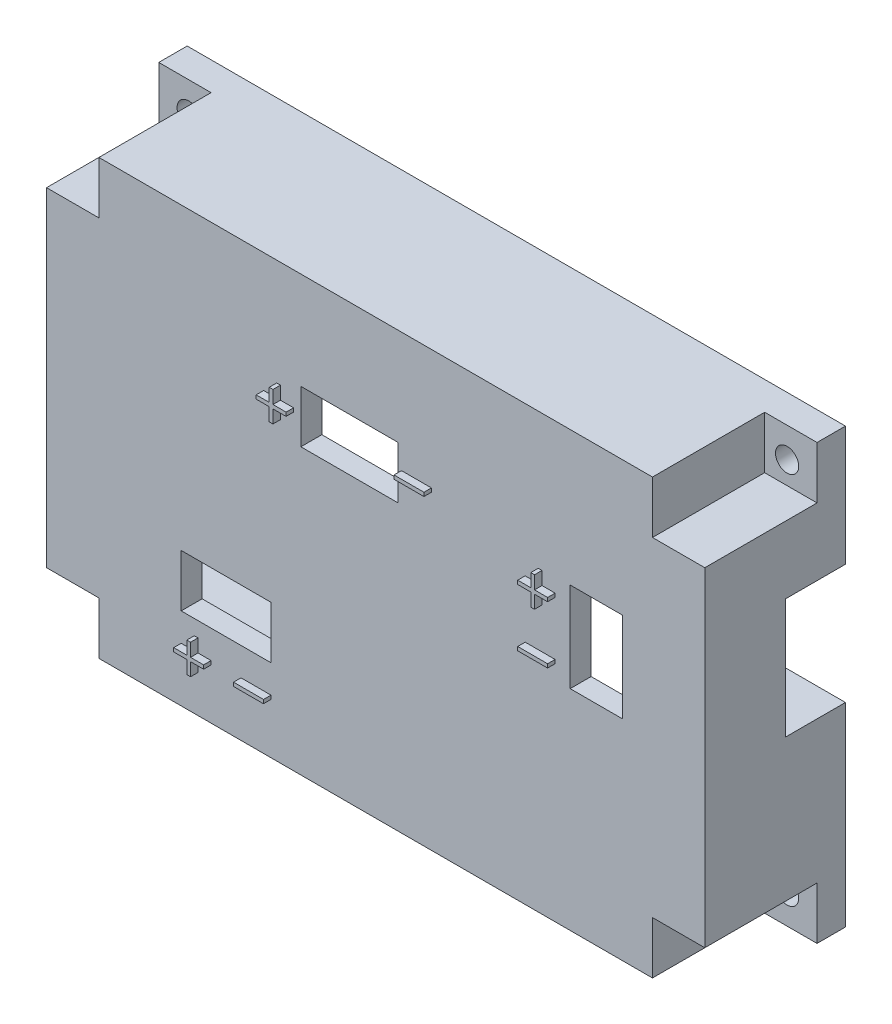
SolidWorks part; units mm, degrees
ref_plane "前视基准面" through (0, 0, 0) normal (0, 0, 1) x (1, 0, 0)
ref_plane "上视基准面" through (0, 0, 0) normal (0, 1, 0) x (1, 0, 0)
ref_plane "右视基准面" through (0, 0, 0) normal (1, 0, 0) x (0, 0, -1)
other "Configuration Table"
sketch "草图1" plane through (0, 0, 0) normal (0, 0, 1) x (1, 0, 0)
  line L1 (0, 58) -> (88, 58)
  line L2 (0, 58) -> (0, 0)
  line L3 (0, 0) -> (88, 0)
  line L4 (88, 58) -> (88, 0)
  dimension "D1" = 88
  dimension "D2" = 58
extrude "凸台-拉伸1" add sketch "草图1" along normal blind 18.8
sketch "草图2" plane through (0, 0, 18.8) normal (0, 0, 1) x (1, 0, 0)
  line L0 (88, 58) -> (0, 58) construction
  line L1 (0, 58) -> (7, 58)
  line L2 (0, 58) -> (0, 51)
  line L3 (0, 51) -> (7, 51)
  line L4 (7, 58) -> (7, 51)
  line L5 (0, 29) -> (88, 29) construction
  line L8 (44, 58) -> (44, 20.983) construction
  line L9 (0, 7) -> (7, 7)
  line L10 (7, 0) -> (7, 7)
  line L11 (0, 0) -> (7, 0)
  line L12 (0, 0) -> (0, 7)
  line L13 (88, 0) -> (88, 7)
  line L14 (88, 0) -> (81, 0)
  line L15 (81, 0) -> (81, 7)
  line L16 (88, 7) -> (81, 7)
  line L17 (88, 51) -> (81, 51)
  line L18 (81, 58) -> (81, 51)
  line L19 (88, 58) -> (81, 58)
  line L20 (88, 58) -> (88, 51)
  dimension "D1" = 7
  dimension "D2" = 7
extrude "切除-拉伸1" cut sketch "草图2" against normal blind 15
sketch "草图3" plane through (0, 0, 3.8) normal (0, 0, 1) x (1, 0, 0)
  line L0 (7, 58) -> (0, 58) construction
  line L1 (0, 58) -> (0, 51) construction
  line L2 (0, 29) -> (42.1109, 29) construction
  line L4 (44, 58) -> (44, 16.8363) construction
  circle A0 centre (4, 54) radius 1.55
  circle A1 centre (4, 4) radius 1.55
  circle A2 centre (84, 4) radius 1.55
  circle A3 centre (84, 54) radius 1.55
  dimension "D1" = 4
  dimension "D2" = 4
extrude "切除-拉伸2" cut sketch "草图3" against normal blind 3
sketch "草图4" plane through (0, 0, 0) normal (0, 0, -1) x (-1, 0, 0)
  line L8 (-8, 8) -> (-8, 50)
  line L9 (-8, 50) -> (-80, 50)
  line L10 (-80, 50) -> (-80, 8)
  line L11 (-80, 8) -> (-8, 8)
  line L12 (-8, 8) -> (-8, 50)
  line L13 (-8, 50) -> (-80, 50)
  line L14 (-80, 50) -> (-80, 8)
  line L15 (-80, 8) -> (-8, 8)
  dimension "D1" = 8
extrude "切除-拉伸6" cut sketch "草图4" against normal blind 16
sketch "草图6" plane through (0, 0, 0) normal (0, -1, 0) x (1, 0, 0)
  line L0 (0, 0) -> (88, 0) construction
  line L1 (16, 8) -> (32, 8)
  line L2 (16, 8) -> (16, 0)
  line L3 (16, 0) -> (32, 0)
  line L4 (32, 8) -> (32, 0)
  line L5 (0, 3.8) -> (0, 18.8) construction
  dimension "D1" = 16
  dimension "D2" = 32
  dimension "D3" = 8
extrude "切除-拉伸7" cut sketch "草图6" against normal blind 8
sketch "草图7" plane through (0, 0, 18.8) normal (0, 0, 1) x (1, 0, 0)
  line L103 (18, 18) -> (30, 18)
  line L104 (18, 18) -> (18, 11)
  line L105 (18, 11) -> (30, 11)
  line L106 (30, 18) -> (30, 11)
  line L107 (70, 40) -> (77, 40)
  line L108 (70, 40) -> (70, 28)
  line L109 (70, 28) -> (77, 28)
  line L110 (77, 40) -> (77, 28)
  line L111 (34, 45) -> (47, 45)
  line L112 (34, 45) -> (34, 38)
  line L113 (34, 38) -> (47, 38)
  line L114 (80, 8) -> (80, 50)
  line L115 (8, 8) -> (80, 8)
  line L116 (8, 50) -> (8, 8)
  line L117 (80, 50) -> (8, 50)
  line L118 (80, 8) -> (80, 50)
  line L119 (8, 8) -> (80, 8)
  line L120 (8, 50) -> (8, 8)
  line L121 (80, 50) -> (8, 50)
  line L122 (47, 45) -> (47, 38)
  dimension "D2" = 10
  dimension "D3" = 22
  dimension "D4" = 3
  dimension "D5" = 10
  dimension "D6" = 10
  dimension "D7" = 22
  dimension "D8" = 3
  dimension "D9" = 10
  dimension "D10" = 26
  dimension "D11" = 39
  dimension "D12" = 5
  dimension "D13" = 12
  dimension "D1" = 8
extrude "切除-拉伸11" cut sketch "草图7" against normal up to next contours L122 L111 L112 L113 | L110 L107 L108 L109 | L104 L103 L106 L105 region at (73.5, 34, 18.8) region at (40.5, 41.5, 18.8)
sketch "草图10" plane through (88, 0, 0) normal (1, 0, 0) x (0, 0, -1)
  line L0 (0, 0) -> (0, 58) construction
  line L1 (-8, 42) -> (0, 42)
  line L2 (-8, 42) -> (-8, 26)
  line L3 (-8, 26) -> (0, 26)
  line L4 (0, 42) -> (0, 26)
  line L5 (-3.8, 58) -> (-18.8, 58) construction
  line L6 (-3.8, 58) -> (0, 58) construction
  point P10 (-1.9, 58)
  dimension "D1" = 16
  dimension "D2" = 32
  dimension "D3" = 8
extrude "切除-拉伸13" cut sketch "草图10" against normal up to next
extrude "切除-拉伸14" cut sketch "草图3<2>" against normal up to next
sketch "草图3<2>" plane through (0, 0, 3.8) normal (0, 0, 1) x (1, 0, 0) same geometry as "草图3"
sketch "草图14" plane through (0, 0, 18.8) normal (0, 0, 1) x (1, 0, 0)
  line L0 (18, 7.25) -> (22, 7.25)
  line L1 (18, 7.25) -> (18, 6.75)
  line L2 (18, 6.75) -> (22, 6.75)
  line L3 (22, 7.25) -> (22, 6.75)
  line L4 (19.75, 9) -> (20.25, 9)
  line L5 (19.75, 9) -> (19.75, 5)
  line L6 (19.75, 5) -> (20.25, 5)
  line L7 (20.25, 9) -> (20.25, 5)
  line L8 (30, 7.25) -> (30, 6.75)
  line L9 (30, 6.75) -> (26, 6.75)
  line L10 (26, 7.25) -> (26, 6.75)
  line L11 (30, 7.25) -> (26, 7.25)
  line L12 (18, 11) -> (30, 11) construction
  line L14 (30, 18) -> (30, 11) construction
  dimension "D1" = 1.75
  dimension "D2" = 2.25
  dimension "D3" = 1.75
  dimension "D4" = 1.75
  dimension "D5" = 6
  dimension "D7" = 4
  dimension "D8" = 2
  dimension "D10" = 0
  dimension "D11" = 4
extrude "凸台-拉伸3" add sketch "草图14" along normal blind 1 contours L7 L4 L5 L0 | L7 L0 L5 L2 | L5 L0 L1 L2 | L0 L7 L2 L3 | L7 L2 L5 L6 | L8 L11 L10 L9 region at (18.875, 7, 18.8) region at (20, 8.125, 18.8) region at (20, 7, 18.8) region at (21.125, 7, 18.8) region at (20, 5.875, 18.8) region at (28, 7, 18.8)
sketch "草图16" plane through (0, 0, 18.8) normal (0, 0, 1) x (1, 0, 0)
  line L0 (63.9826, 38.0504) -> (67.9826, 38.0504)
  line L1 (63.9826, 38.0504) -> (63.9826, 37.5504)
  line L2 (63.9826, 37.5504) -> (67.9826, 37.5504)
  line L3 (67.9826, 38.0504) -> (67.9826, 37.5504)
  line L4 (65.7326, 39.8004) -> (66.2326, 39.8004)
  line L5 (65.7326, 39.8004) -> (65.7326, 35.8004)
  line L6 (65.7326, 35.8004) -> (66.2326, 35.8004)
  line L7 (66.2326, 39.8004) -> (66.2326, 35.8004)
  line L8 (67.9826, 30.3734) -> (67.9826, 29.8734)
  line L9 (67.9826, 29.8734) -> (63.9826, 29.8734)
  line L10 (63.9826, 30.3734) -> (63.9826, 29.8734)
  line L11 (67.9826, 30.3734) -> (63.9826, 30.3734)
  point P20 (37.475, 37.9532)
  dimension "D1" = 1.75
  dimension "D2" = 4
  dimension "D3" = 4
extrude "凸台-拉伸5" add sketch "草图16" along normal blind 1 contours L0 L7 L2 L3 | L7 L4 L5 L0 | L7 L2 L5 L6 | L8 L11 L10 L9 | L0 L3 L2 L1 region at (65.9826, 38.9254, 18.8) region at (67.1076, 37.8004, 18.8) region at (65.9826, 36.6754, 18.8) region at (65.9826, 30.1234, 18.8)
sketch "草图18" plane through (0, 0, 18.8) normal (0, 0, 1) x (1, 0, 0)
  line L0 (29.0208, 42.0256) -> (33.0208, 42.0256)
  line L1 (29.0208, 42.0256) -> (29.0208, 41.5256)
  line L2 (29.0208, 41.5256) -> (33.0208, 41.5256)
  line L3 (33.0208, 42.0256) -> (33.0208, 41.5256)
  line L4 (30.7708, 43.7756) -> (31.2708, 43.7756)
  line L5 (30.7708, 43.7756) -> (30.7708, 39.7756)
  line L6 (30.7708, 39.7756) -> (31.2708, 39.7756)
  line L7 (31.2708, 43.7756) -> (31.2708, 39.7756)
  line L8 (51.4515, 41.965) -> (51.4515, 41.465)
  line L9 (51.4515, 41.465) -> (47.4515, 41.465)
  line L10 (47.4515, 41.965) -> (47.4515, 41.465)
  line L11 (51.4515, 41.965) -> (47.4515, 41.965)
  dimension "D1" = 4
extrude "凸台-拉伸6" add sketch "草图18" along normal blind 1 contours L8 L11 L10 L9 | L7 L4 L5 L0 | L7 L2 L5 L6 | L2 L3 L0 L1 region at (31.0208, 42.9006, 18.8) region at (31.0208, 40.6506, 18.8) region at (49.4515, 41.715, 18.8)
